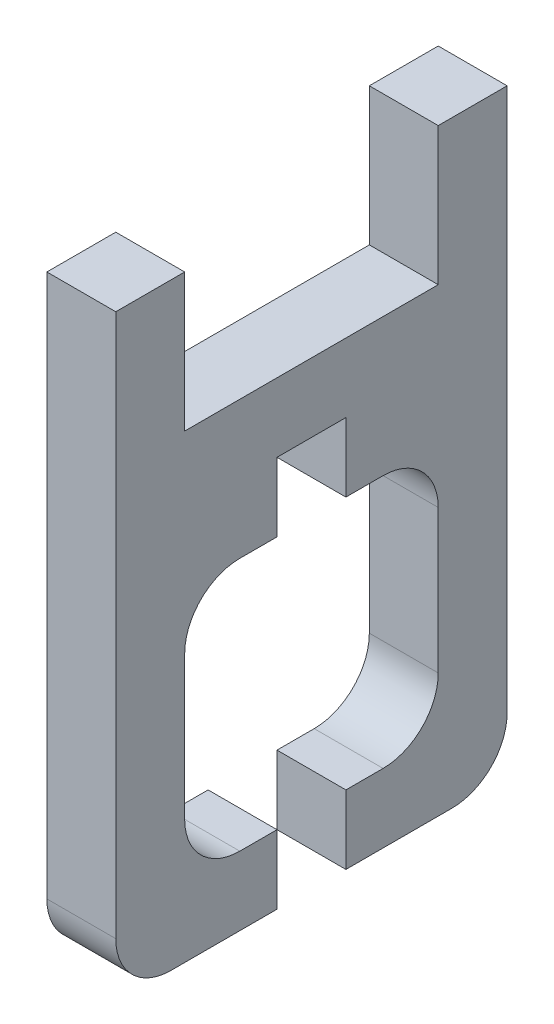
SolidWorks part; units mm, degrees
material "Pine"
ref_plane "Front Plane" through (0, 0, 0) normal (0, 0, 1) x (1, 0, 0)
ref_plane "Top Plane" through (0, 0, 0) normal (0, 1, 0) x (1, 0, 0)
ref_plane "Right Plane" through (0, 0, 0) normal (1, 0, 0) x (0, 0, -1)
sketch "Sketch2" plane through (0, 0, 0) normal (1, 0, 0) x (0, 0, -1)
  line L7 (30.988, 0) -> (5.08, 0)
  line L9 (11.43, 6.35) -> (24.638, 6.35)
  line L10 (6.35, 11.43) -> (6.35, 24.638)
  line L12 (29.718, 11.43) -> (29.718, 24.638)
  line L18 (36.068, 36.068) -> (36.068, 5.08)
  line L21 (0, 36.068) -> (0, 5.08)
  line L24 (24.638, 29.718) -> (21.209, 29.718)
  line L25 (21.209, 29.718) -> (21.209, 36.068)
  line L26 (21.209, 36.068) -> (14.859, 36.068)
  line L27 (14.859, 36.068) -> (14.859, 29.718)
  line L28 (14.859, 29.718) -> (11.43, 29.718)
  line L29 (0, 36.068) -> (0, 55.118)
  line L30 (14.859, 6.35) -> (21.209, 6.35)
  line L31 (14.859, 6.35) -> (14.859, 0)
  line L32 (14.859, 0) -> (21.209, 0)
  line L33 (21.209, 6.35) -> (21.209, 0)
  line L34 (0, 55.118) -> (6.35, 55.118)
  line L35 (6.35, 55.118) -> (6.35, 42.418)
  line L39 (36.068, 55.118) -> (36.068, 36.068)
  line L40 (36.068, 55.118) -> (29.718, 55.118)
  line L41 (29.718, 55.118) -> (29.718, 42.418)
  line L42 (29.718, 42.418) -> (6.35, 42.418)
  arc A0 (11.43, 6.35) -> (6.35, 11.43) centre (11.43, 11.43) cw
  arc A1 (24.638, 6.35) -> (29.718, 11.43) centre (24.638, 11.43) ccw
  arc A2 (24.638, 29.718) -> (29.718, 24.638) centre (24.638, 24.638) cw
  arc A3 (6.35, 24.638) -> (11.43, 29.718) centre (11.43, 24.638) cw
  arc A4 (36.068, 5.08) -> (30.988, 0) centre (30.988, 5.08) cw
  arc A5 (0, 5.08) -> (5.08, 0) centre (5.08, 5.08) ccw
  point P13 (18.034, 42.418)
  point P16 (18.034, 0)
  point P26 (18.034, 0)
  point P30 (6.35, 6.35)
  point P35 (29.718, 29.718)
  point P38 (6.35, 29.718)
  point P43 (0, 0)
  dimension "D15" = 5.08
  dimension "D16" = 5.08
  dimension "D2" = 23.368
  dimension "D3" = 23.368
  dimension "D4" = 6.35
  dimension "D9" = 6.35
  dimension "D10" = 6.35
  dimension "D7" = 6.35
  dimension "D8" = 6.35
  dimension "D14" = 6.35
  dimension "D5" = 6.35
  dimension "D6" = 6.35
extrude "Boss-Extrude1" add sketch "Sketch2" along normal blind 6.35 contours L9 L33 L7 L18 L41 L21 L31 L10 L28 L27 L26 L25 L24 L12 region at (0, 0.6587, -26.0985)
equation "\"D2@Sketch2\"=\"D3@Sketch2\""
